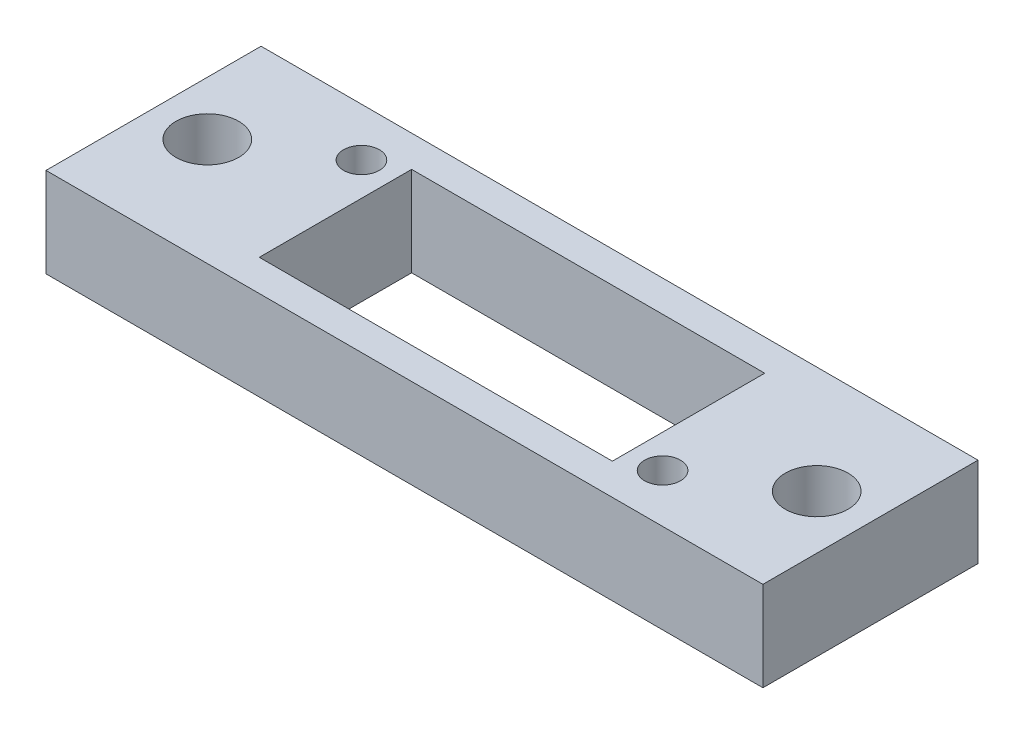
SolidWorks part; units mm, degrees
ref_plane "Front Plane" through (0, 0, 0) normal (0, 0, 1) x (1, 0, 0)
ref_plane "Top Plane" through (0, 0, 0) normal (0, 1, 0) x (1, 0, 0)
ref_plane "Right Plane" through (0, 0, 0) normal (1, 0, 0) x (0, 0, -1)
sketch "스케치1" plane through (0, 0, 0) normal (0, 1, 0) x (1, 0, 0)
  line L1 (-20, 6) -> (20, 6)
  line L2 (-20, 6) -> (-20, -6)
  line L3 (-20, -6) -> (20, -6)
  line L4 (20, 6) -> (20, -6)
  dimension "D1" = 20
  dimension "D2" = 40
  dimension "D3" = 12
  dimension "D4" = 6
extrude "보스-돌출1" add sketch "스케치1" along normal blind 5
sketch "스케치2" plane through (0, 5, 0) normal (0, 1, 0) x (1, 0, 0)
  line L1 (-9.85, 4.25) -> (9.85, 4.25)
  line L2 (-9.85, 4.25) -> (-9.85, -4.25)
  line L3 (-9.85, -4.25) -> (9.85, -4.25)
  line L4 (9.85, 4.25) -> (9.85, -4.25)
  dimension "D1" = 19.7
  dimension "D2" = 8.5
  dimension "D3" = 4.25
  dimension "D4" = 9.85
extrude "컷-돌출1" cut sketch "스케치2" against normal blind 5
sketch "스케치3" plane through (0, 5, 0) normal (0, 1, 0) x (1, 0, 0)
  line L0 (-16.0674, 3.3) -> (49983.9326, 3.3) construction
  line L1 (-16.4671, -3.3) -> (49983.5329, -3.3) construction
  line L2 (-11.7, 0.2598) -> (-11.7, -49999.7402) construction
  line L3 (11.7, 1.259) -> (11.7, -49998.741) construction
  line L6 (0, 0) -> (-50000, 0) construction
  circle A0 centre (-11.7, 3.3) radius 1
  circle A1 centre (11.7, -3.3) radius 1
  dimension "D1" = 3.3
  dimension "D2" = 3.3
  dimension "D3" = 11.7
  dimension "D4" = 11.7
extrude "컷-돌출2" cut sketch "스케치3" against normal blind 5
sketch "스케치4" plane through (0, 5, 0) normal (0, 1, 0) x (1, 0, 0)
  line L0 (0, 0) -> (50000, 0) construction
  line L1 (-17, 0) -> (-17, -50000) construction
  line L2 (17, 0) -> (17, -50000) construction
  circle A0 centre (-17, 0) radius 1.75
  circle A1 centre (17, 0) radius 1.75
  dimension "D1" = 17
  dimension "D2" = 17
extrude "컷-돌출3" cut sketch "스케치4" against normal blind 10
